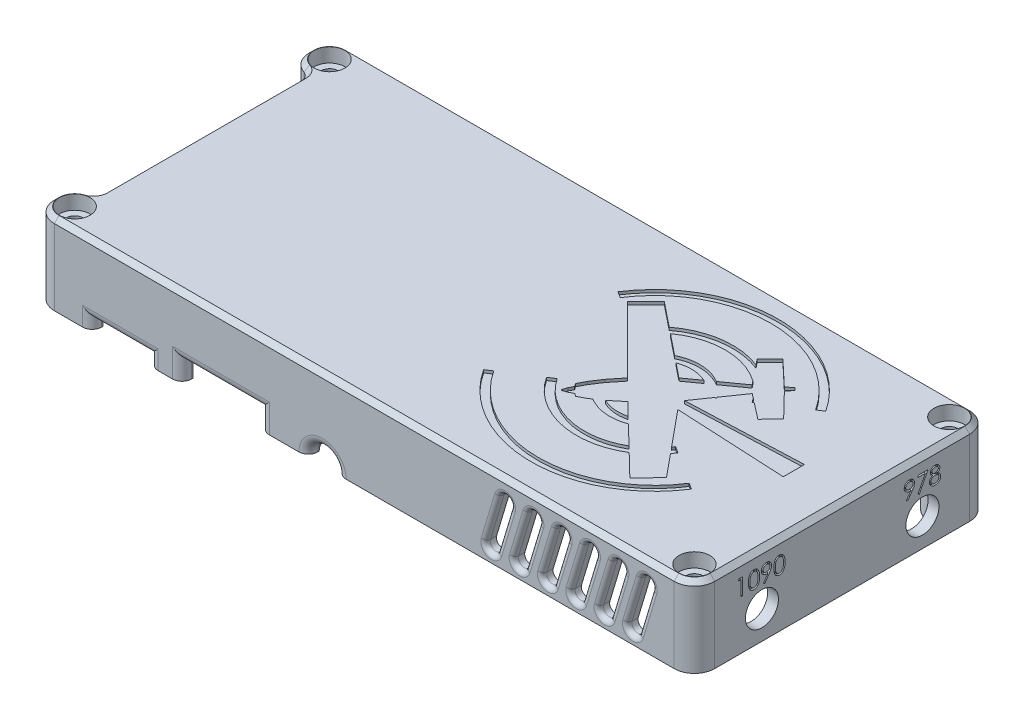
SolidWorks part; units mm, degrees
ref_plane "Front Plane" through (0, 0, 0) normal (0, 0, 1) x (1, 0, 0)
ref_plane "Top Plane" through (0, 0, 0) normal (0, 1, 0) x (1, 0, 0)
ref_plane "Right Plane" through (0, 0, 0) normal (1, 0, 0) x (0, 0, -1)
sketch "Sketch1" plane through (0, 0, 0) normal (0, 1, 0) x (1, 0, 0)
  line L0 (-71.5618, 3.106) -> (57.4382, 3.106) construction
  line L1 (-71.5618, 31.106) -> (57.4382, 31.106)
  line L2 (-71.5618, 31.106) -> (-71.5618, -24.894)
  line L3 (-71.5618, -24.894) -> (57.4382, -24.894)
  line L4 (57.4382, 31.106) -> (57.4382, -24.894)
  line L5 (-60.6618, -24.894) -> (-60.6618, -31.6828) construction
  line L6 (-68.0618, 27.606) -> (-10.0618, 27.606)
  line L7 (-68.0618, 27.606) -> (-68.0618, -21.394)
  line L8 (-68.0618, -21.394) -> (-10.0618, -21.394)
  line L9 (-10.0618, 27.606) -> (-10.0618, -21.394)
  line L10 (-39.5618, -24.894) -> (-39.5618, -31.6828) construction
  line L11 (-18.0618, -24.894) -> (-18.0618, -31.6828) construction
  line L12 (-65.4118, -26.5648) -> (-55.9118, -26.5648) construction
  line L13 (-48.0618, -26.5648) -> (-31.0618, -26.5648) construction
  line L14 (-22.0618, -26.5648) -> (-14.0618, -26.5648) construction
  line L15 (-72.5618, 9.606) -> (-72.5618, -3.394) construction
  line L16 (-71.5618, 3.106) -> (-72.5618, 3.106) construction
  line L17 (-60.6618, -24.894) -> (-60.6618, 40.2849) construction
  dimension "D1" = 129
  dimension "D2" = 56
  dimension "D3" = 49
  dimension "D4" = 58
  dimension "D5" = 3.5
  dimension "D6" = 3.5
  dimension "D7" = 10.9
  dimension "D8" = 32
  dimension "D9" = 53.5
  dimension "D10" = 2
  dimension "D11" = 13
  dimension "D12" = 9.5
  dimension "D13" = 17
  dimension "D14" = 8
sketch "Sketch3" plane through (0, 0, 0) normal (0, 1, 0) x (1, 0, 0)
  line L2 (-72.5618, -25.894) -> (58.4382, -25.894) construction
  line L3 (60.7382, -28.194) -> (60.7382, 34.406) construction
  line L4 (60.7382, 34.406) -> (-74.8618, 34.406)
  line L5 (-74.8618, 34.406) -> (-74.8618, -28.194)
  line L6 (-74.8618, -28.194) -> (60.7382, -28.194)
  line L8 (58.4382, 32.106) -> (-72.5618, 32.106)
  line L9 (58.4382, -25.894) -> (58.4382, 32.106)
  line L10 (-72.5618, -25.894) -> (58.4382, -25.894)
  line L11 (-72.5618, 32.106) -> (-72.5618, -25.894)
  line L12 (58.4382, 32.106) -> (-72.5618, 32.106)
  line L13 (58.4382, -25.894) -> (58.4382, 32.106)
  line L14 (-72.5618, -25.894) -> (58.4382, -25.894)
  line L15 (-72.5618, 32.106) -> (-72.5618, -25.894)
  line L16 (-7.0618, 3.106) -> (-7.0618, 34.406) construction
  line L17 (-71.5618, 3.106) -> (57.4382, 3.106) construction
  line L18 (58.4382, -25.894) -> (58.4382, 32.106) construction
  line L20 (-74.8618, 3.106) -> (52.7382, 3.106) construction
  line L22 (-74.8618, -28.194) -> (60.7382, -28.194) construction
  line L23 (60.7382, -28.194) -> (60.7382, 34.406)
  dimension "D1" = 1
  dimension "D2" = 2.3
extrude "Boss-Extrude1" add sketch "Sketch3" along normal blind 17
sketch "Sketch5" plane through (0, 0, 0) normal (0, 1, 0) x (1, 0, 0)
  line L1 (-72.5618, 32.106) -> (58.4382, 32.106)
  line L2 (-72.5618, 32.106) -> (-72.5618, -25.894)
  line L3 (-72.5618, -25.894) -> (58.4382, -25.894)
  line L4 (58.4382, 32.106) -> (58.4382, -25.894)
sketch "Sketch11" plane through (0, 0, 28.194) normal (0, 0, 1) x (1, 0, 0)
  line L0 (-74.8618, 17) -> (-74.8618, 0) construction
  line L2 (-66.8618, 0) -> (-54.8618, 0)
  line L3 (-66.8618, 0) -> (-66.8618, 2)
  line L4 (-66.8618, 2) -> (-54.8618, 2)
  line L5 (-54.8618, 0) -> (-54.8618, 2)
  line L9 (-47.8118, 4) -> (-31.3118, 4)
  line L10 (-47.8118, 4) -> (-47.8118, 0)
  line L11 (-47.8118, 0) -> (-31.3118, 0)
  line L12 (-31.3118, 4) -> (-31.3118, 0)
  line L14 (-39.5618, 0) -> (-39.528, 10.3) construction
  line L15 (-48.0618, 0) -> (-31.0618, 0) construction
  line L16 (-18.0618, 0) -> (-18.0618, 10.3) construction
  line L17 (-22.0618, 0) -> (-14.0618, 0) construction
  circle A0 centre (-18.0618, 0) radius 3
  dimension "D5" = 6
  dimension "D1" = 4
  dimension "D2" = 2
  dimension "D3" = 12
  dimension "D4" = 16.5
  dimension "D7" = 8
extrude "Cut-Extrude1" cut sketch "Sketch11" against normal up to next
sketch "Sketch14" plane through (0, 0, 0) normal (0, -1, 0) x (1, 0, 0)
  line L1 (-74.8618, 11.894) -> (-72.5618, 11.894)
  line L2 (-74.8618, 11.894) -> (-74.8618, -18.106)
  line L3 (-74.8618, -18.106) -> (-72.5618, -18.106)
  line L4 (-72.5618, 11.894) -> (-72.5618, -18.106)
  dimension "D1" = 30
extrude "Boss-Extrude6" add sketch "Sketch14" along normal blind 2.8
fillet "Fillet6" radius 2 4 edges at (-18.0618, 3, 28.194) (-31.3118, 2, 28.194) (-39.5618, 4, 28.194) (-47.8118, 2, 28.194)
sketch "Sketch15" plane through (-74.8618, 0, 0) normal (-1, 0, 0) x (0, 0, 1)
  line L1 (-9.7403, -3.6489) -> (3.7597, -3.6489)
  line L2 (-9.7403, -3.6489) -> (-9.7403, -2.6489)
  line L3 (-9.7403, -2.6489) -> (3.7597, -2.6489)
  line L4 (3.7597, -3.6489) -> (3.7597, -2.6489)
extrude "Cut-Extrude3" cut sketch "Sketch15" against normal up to next
fillet "Fillet8" radius 2 3 edges at (-74.8618, -2.7245, 3.7597) (-74.8618, -2.7245, -9.7403) (-74.8618, -2.6489, -2.9903)
sketch "Sketch35" plane through (0, 17, 0) normal (0, 1, 0) x (1, 0, 0)
  line L1 (-72.5618, 32.106) -> (58.4382, 32.106)
  line L2 (-72.5618, 32.106) -> (-72.5618, -25.894)
  line L3 (-72.5618, -25.894) -> (58.4382, -25.894)
  line L4 (58.4382, 32.106) -> (58.4382, -25.894)
extrude "Boss-Extrude7" add sketch "Sketch35" against normal blind 2
sketch "Sketch36" plane through (0, 17, 0) normal (0, 1, 0) x (1, 0, 0)
  line L0 (13.7863, -0.484) -> (12.349, -1.4216)
  line L1 (26.8986, -0.4563) -> (28.3399, -1.3879)
  line L2 (13.7684, 8.0304) -> (12.3271, 8.962)
  line L3 (26.8807, 8.058) -> (28.318, 8.9957)
  line L4 (41.0203, -9.5839) -> (42.3245, -10.4269)
  line L5 (32.8559, -4.3068) -> (34.2397, -5.2013)
  line L6 (7.8454, -4.3595) -> (6.4653, -5.2598)
  line L7 (-0.2967, -9.6709) -> (-1.5974, -10.5194)
  line L8 (-0.3532, 17.158) -> (-1.6575, 18.001)
  line L9 (7.8112, 11.8809) -> (6.4273, 12.7754)
  line L10 (32.8217, 11.9336) -> (34.2017, 12.8338)
  line L11 (40.9638, 17.245) -> (42.2645, 18.0935)
  line L12 (49.7971, 1.5668) -> (22.6747, 2.9133)
  line L13 (49.7971, 6.0552) -> (22.6747, 4.9652)
  line L14 (49.7971, 1.5668) -> (49.7971, 6.0552)
  line L15 (22.6747, 2.9133) -> (22.6747, 4.9652)
  arc A0 (42.2645, 18.0935) -> (-1.6575, 18.001) centre (20.3335, 3.787) ccw
  arc A1 (40.9638, 17.245) -> (-0.3532, 17.158) centre (20.3335, 3.787) ccw
  arc A2 (26.8807, 8.058) -> (13.7684, 8.0304) centre (20.3335, 3.787) ccw
  arc A3 (28.318, 8.9957) -> (12.3271, 8.962) centre (20.3335, 3.787) ccw
  arc A4 (34.2017, 12.8338) -> (6.4273, 12.7754) centre (20.3335, 3.787) ccw
  arc A5 (32.8217, 11.9336) -> (7.8112, 11.8809) centre (20.3335, 3.787) ccw
  arc A6 (-1.5974, -10.5194) -> (42.3245, -10.4269) centre (20.3335, 3.787) ccw
  arc A7 (-0.2967, -9.6709) -> (41.0203, -9.5839) centre (20.3335, 3.787) ccw
  arc A8 (6.4653, -5.2598) -> (34.2397, -5.2013) centre (20.3335, 3.787) ccw
  arc A9 (7.8454, -4.3595) -> (32.8559, -4.3068) centre (20.3335, 3.787) ccw
  arc A10 (12.349, -1.4216) -> (28.3399, -1.3879) centre (20.3335, 3.787) ccw
  arc A11 (13.7863, -0.484) -> (26.8986, -0.4563) centre (20.3335, 3.787) ccw
extrude "Cut-Extrude4" cut sketch "Sketch36" against normal blind 0.6
sketch "Sketch37" plane through (0, 17, 0) normal (0, 1, 0) x (1, 0, 0)
  line L0 (19.5432, -1.113) -> (33.7651, -14.904)
  line L1 (33.7651, -14.904) -> (37.5849, -10.9649)
  line L2 (37.5849, -10.9649) -> (24.9049, 4.4162)
  line L3 (24.9049, 4.4162) -> (31.2449, 13.5399)
  line L4 (31.2449, 13.5399) -> (36.5589, 9.4198)
  line L5 (36.5589, 9.4198) -> (39.2481, 12.193)
  line L6 (39.2481, 12.193) -> (34.218, 17.3746)
  line L7 (34.218, 17.3746) -> (35.2171, 18.6632)
  line L8 (35.2171, 18.6632) -> (34.9302, 18.8856)
  line L9 (19.5432, -1.113) -> (16.9215, -3.2743)
  line L10 (16.9215, -3.2743) -> (14.6893, -4.7957)
  line L11 (14.6893, -4.7957) -> (13.0543, -5.6738)
  line L12 (13.0543, -5.6738) -> (12.4225, -5.2348)
  line L13 (12.4225, -5.2348) -> (11.4673, -5.7477)
  line L14 (11.4673, -5.7477) -> (10.605, -6.0351)
  line L15 (10.605, -6.0351) -> (10.3641, -6.0351)
  line L16 (34.9302, 18.8856) -> (10.3641, -6.0351) construction
  line L17 (10.3607, -5.7943) -> (10.3641, -6.0351)
  line L18 (10.6357, -4.9279) -> (10.3607, -5.7943)
  line L19 (11.1349, -3.9655) -> (10.6357, -4.9279)
  line L20 (10.6869, -3.3401) -> (11.1349, -3.9655)
  line L21 (11.5414, -1.6927) -> (10.6869, -3.3401)
  line L22 (13.0306, 0.5611) -> (11.5414, -1.6927)
  line L23 (15.1541, 3.2135) -> (13.0306, 0.5611)
  line L24 (34.7036, 19.1694) -> (34.9302, 18.8856)
  line L25 (33.4295, 18.1519) -> (34.7036, 19.1694)
  line L26 (28.1763, 23.1072) -> (33.4295, 18.1519)
  line L27 (25.4419, 20.3785) -> (28.1763, 23.1072)
  line L28 (29.6378, 15.1241) -> (25.4419, 20.3785)
  line L29 (20.6059, 8.6539) -> (29.6378, 15.1241)
  line L30 (5.0446, 21.1121) -> (20.6059, 8.6539)
  line L31 (1.1607, 17.2363) -> (5.0446, 21.1121)
  line L32 (15.1541, 3.2135) -> (1.1607, 17.2363)
extrude "Cut-Extrude5" cut sketch "Sketch37" against normal blind 0.6
sketch "Sketch48" plane through (0, 17, 0) normal (0, 1, 0) x (1, 0, 0)
  line L0 (-74.8618, -19.594) -> (-74.8618, -28.194)
  line L1 (-74.8618, 34.406) -> (-74.8618, 25.806)
  line L2 (-74.8618, 3.106) -> (-35.5735, 3.106) construction
  line L3 (-74.8618, 34.406) -> (-74.8618, -28.194) construction
  line L4 (60.7382, -28.194) -> (60.7382, 34.406) construction
  arc A0 (-74.8618, -28.194) -> (-74.8618, -19.594) centre (-74.8618, -23.894) cw
  arc A1 (-74.8618, 25.806) -> (-74.8618, 34.406) centre (-74.8618, 30.106) cw
  circle A2 centre (56.4382, 30.106) radius 4.3
  circle A3 centre (56.4382, -23.894) radius 4.3
  dimension "D1" = 4.3
extrude "Boss-Extrude9" add sketch "Sketch48" against normal up to vertex
hole_wizard "CBORE for M3 SHCS1" positions "Sketch50" profile "Sketch49" counterbore size "M3" standard "ANSI Metric" end condition up to next
sketch "Sketch50" plane through (0, 17, 0) normal (0, 1, 0) x (1, 0, 0)
  point P0 (-74.8618, 30.106)
sketch "Sketch49" plane through (-74.8618, 17, -30.106) normal (1, 0, 0) x (0, 0, 1)
  line L0 (0, 0) -> (0, 17)
  line L1 (0, 17) -> (1.8, 17)
  line L3 (1.8, 17) -> (1.8, 3)
  line L4 (1.8, 3) -> (3.25, 3)
  line L5 (3.25, 3) -> (3.25, 0)
  line L7 (3.25, 0) -> (0, 0)
  line L11 (0, -6.35) -> (0, 107.95) construction
  dimension "Thru Hole Dia." = 3.6
  dimension "Thru Hole Depth" = 17
  dimension "C'Bore Dia." = 6.5
  dimension "C'Bore Depth" = 3
hole_wizard "CBORE for M3 SHCS2" positions "Sketch52" profile "Sketch51" counterbore size "M3" standard "ANSI Metric" end condition up to next
sketch "Sketch52" plane through (0, 17, 0) normal (0, 1, 0) x (1, 0, 0)
  point P0 (-74.8618, -23.894)
sketch "Sketch51" plane through (-74.8618, 17, 23.894) normal (1, 0, 0) x (0, 0, 1)
  line L0 (0, 0) -> (0, 17)
  line L1 (0, 17) -> (1.8, 17)
  line L3 (1.8, 17) -> (1.8, 3)
  line L4 (1.8, 3) -> (3.25, 3)
  line L5 (3.25, 3) -> (3.25, 0)
  line L7 (3.25, 0) -> (0, 0)
  line L11 (0, -6.35) -> (0, 107.95) construction
  dimension "Thru Hole Dia." = 3.6
  dimension "Thru Hole Depth" = 17
  dimension "C'Bore Dia." = 6.5
  dimension "C'Bore Depth" = 3
fillet "Fillet13" radius 2 2 edges at (-74.8618, 8.5, 19.594) (-74.8618, 8.5, -25.806)
chamfer "Chamfer1" distance 1 angle 45 1 edges at (-9.8342, 15, -32.106)
chamfer "Chamfer3" distance 1 angle 45 7 edges at (-7.0618, 17, -34.406) (-79.1058, 17, -30.7975) (-74.8618, 17, -3.106) (-79.1058, 17, 24.5855) (-75.2385, 17, 19.0883) (-75.2385, 17, -25.3002) (-7.0618, 17, 28.194)
fillet "Fillet14" radius 2 3 edges at (-66.8618, 1, 28.194) (-60.8618, 2, 28.194) (-54.8618, 1, 28.194)
sketch "Sketch58" plane through (-74.8618, 0, 0) normal (-1, 0, 0) x (0, 0, 1)
  line L0 (-19.9832, 3.4697) -> (-16.3616, 12.7909) construction
  line L1 (-21.1484, 3.9224) -> (-17.5268, 13.2436)
  line L2 (-18.8181, 3.017) -> (-15.1965, 12.3382)
  line L3 (-13.9832, 3.4697) -> (-10.3616, 12.7909) construction
  line L4 (-15.1484, 3.9224) -> (-11.5268, 13.2436)
  line L5 (-12.8181, 3.017) -> (-9.1965, 12.3382)
  line L6 (-7.9832, 3.4697) -> (-4.3616, 12.7909) construction
  line L7 (-9.1484, 3.9224) -> (-5.5268, 13.2436)
  line L8 (-6.8181, 3.017) -> (-3.1965, 12.3382)
  line L9 (-1.9832, 3.4697) -> (1.6384, 12.7909) construction
  line L10 (-3.1484, 3.9224) -> (0.4732, 13.2436)
  line L11 (-0.8181, 3.017) -> (2.8035, 12.3382)
  line L12 (4.0168, 3.4697) -> (7.6384, 12.7909) construction
  line L13 (2.8516, 3.9224) -> (6.4732, 13.2436)
  line L14 (5.1819, 3.017) -> (8.8035, 12.3382)
  line L15 (10.0168, 3.4697) -> (13.6384, 12.7909) construction
  line L16 (8.8516, 3.9224) -> (12.4732, 13.2436)
  line L17 (11.1819, 3.017) -> (14.8035, 12.3382)
  arc A0 (-21.1484, 3.9224) -> (-18.8181, 3.017) centre (-19.9832, 3.4697) ccw
  arc A1 (-15.1965, 12.3382) -> (-17.5268, 13.2436) centre (-16.3616, 12.7909) ccw
  arc A2 (-15.1484, 3.9224) -> (-12.8181, 3.017) centre (-13.9832, 3.4697) ccw
  arc A3 (-9.1965, 12.3382) -> (-11.5268, 13.2436) centre (-10.3616, 12.7909) ccw
  arc A4 (-9.1484, 3.9224) -> (-6.8181, 3.017) centre (-7.9832, 3.4697) ccw
  arc A5 (-3.1965, 12.3382) -> (-5.5268, 13.2436) centre (-4.3616, 12.7909) ccw
  arc A6 (-3.1484, 3.9224) -> (-0.8181, 3.017) centre (-1.9832, 3.4697) ccw
  arc A7 (2.8035, 12.3382) -> (0.4732, 13.2436) centre (1.6384, 12.7909) ccw
  arc A8 (2.8516, 3.9224) -> (5.1819, 3.017) centre (4.0168, 3.4697) ccw
  arc A9 (8.8035, 12.3382) -> (6.4732, 13.2436) centre (7.6384, 12.7909) ccw
  arc A10 (8.8516, 3.9224) -> (11.1819, 3.017) centre (10.0168, 3.4697) ccw
  arc A11 (14.8035, 12.3382) -> (12.4732, 13.2436) centre (13.6384, 12.7909) ccw
  point P2 (-18.1724, 8.1303)
  point P10 (-12.1724, 8.1303)
  point P17 (-6.1724, 8.1303)
  point P24 (-0.1724, 8.1303)
  point P31 (5.8276, 8.1303)
  point P38 (11.8276, 8.1303)
  dimension "D1" = 6
fillet "Fillet15" radius 4.3 2 edges at (60.7382, 8, -34.406) (60.7382, 8, 28.194)
hole_wizard "CBORE for M3 SHCS4" positions "Sketch62" profile "Sketch61" counterbore size "M3" standard "ANSI Metric" end condition up to next
sketch "Sketch62" plane through (0, 17, 0) normal (0, 1, 0) x (1, 0, 0)
  point P0 (56.4382, 30.106)
sketch "Sketch61" plane through (56.4382, 17, -30.106) normal (1, 0, 0) x (0, 0, 1)
  line L0 (0, 0) -> (0, 17)
  line L1 (0, 17) -> (1.8, 17)
  line L3 (1.8, 17) -> (1.8, 3)
  line L4 (1.8, 3) -> (3.25, 3)
  line L5 (3.25, 3) -> (3.25, 0)
  line L7 (3.25, 0) -> (0, 0)
  line L11 (0, -6.35) -> (0, 107.95) construction
  dimension "Thru Hole Dia." = 3.6
  dimension "Thru Hole Depth" = 17
  dimension "C'Bore Dia." = 6.5
  dimension "C'Bore Depth" = 3
hole_wizard "CBORE for M3 SHCS5" positions "Sketch64" profile "Sketch63" counterbore size "M3" standard "ANSI Metric" end condition up to next
sketch "Sketch64" plane through (0, 17, 0) normal (0, 1, 0) x (1, 0, 0)
  point P0 (56.4382, -23.894)
sketch "Sketch63" plane through (56.4382, 17, 23.894) normal (1, 0, 0) x (0, 0, 1)
  line L0 (0, 0) -> (0, 17)
  line L1 (0, 17) -> (1.8, 17)
  line L3 (1.8, 17) -> (1.8, 3)
  line L4 (1.8, 3) -> (3.25, 3)
  line L5 (3.25, 3) -> (3.25, 0)
  line L7 (3.25, 0) -> (0, 0)
  line L11 (0, -6.35) -> (0, 107.95) construction
  dimension "Thru Hole Dia." = 3.6
  dimension "Thru Hole Depth" = 17
  dimension "C'Bore Dia." = 6.5
  dimension "C'Bore Depth" = 3
chamfer "Chamfer7" distance 1 angle 45 5 edges at (60.7382, 17, -3.106) (60.3334, 17, 25.7155) (60.3334, 17, -31.9275) (57.9045, 16.2577, -34.1483) (57.9045, 16.2577, 27.9363)
sketch "Sketch67" plane through (0, 0, 28.194) normal (0, 0, 1) x (1, 0, 0)
  line L0 (44.5955, 12.4849) -> (41.7225, 2.9065) construction
  line L1 (45.7928, 12.1258) -> (42.9198, 2.5474)
  line L2 (43.3981, 12.8441) -> (40.5252, 3.2656)
  line L3 (38.5955, 12.4849) -> (35.7225, 2.9065) construction
  line L4 (39.7928, 12.1258) -> (36.9198, 2.5474)
  line L5 (37.3981, 12.8441) -> (34.5252, 3.2656)
  line L6 (32.5955, 12.4849) -> (29.7225, 2.9065) construction
  line L7 (33.7928, 12.1258) -> (30.9198, 2.5474)
  line L8 (31.3981, 12.8441) -> (28.5252, 3.2656)
  line L9 (26.5955, 12.4849) -> (23.7225, 2.9065) construction
  line L10 (27.7928, 12.1258) -> (24.9198, 2.5474)
  line L11 (25.3981, 12.8441) -> (22.5252, 3.2656)
  line L12 (50.5955, 12.4849) -> (47.7225, 2.9065) construction
  line L13 (51.7928, 12.1258) -> (48.9198, 2.5474)
  line L14 (49.3981, 12.8441) -> (46.5252, 3.2656)
  line L15 (20.5955, 12.4849) -> (17.7225, 2.9065) construction
  line L16 (21.7928, 12.1258) -> (18.9198, 2.5474)
  line L17 (19.3981, 12.8441) -> (16.5252, 3.2656)
  arc A0 (45.7928, 12.1258) -> (43.3981, 12.8441) centre (44.5955, 12.4849) ccw
  arc A1 (40.5252, 3.2656) -> (42.9198, 2.5474) centre (41.7225, 2.9065) ccw
  arc A2 (39.7928, 12.1258) -> (37.3981, 12.8441) centre (38.5955, 12.4849) ccw
  arc A3 (34.5252, 3.2656) -> (36.9198, 2.5474) centre (35.7225, 2.9065) ccw
  arc A4 (33.7928, 12.1258) -> (31.3981, 12.8441) centre (32.5955, 12.4849) ccw
  arc A5 (28.5252, 3.2656) -> (30.9198, 2.5474) centre (29.7225, 2.9065) ccw
  arc A6 (27.7928, 12.1258) -> (25.3981, 12.8441) centre (26.5955, 12.4849) ccw
  arc A7 (22.5252, 3.2656) -> (24.9198, 2.5474) centre (23.7225, 2.9065) ccw
  arc A8 (51.7928, 12.1258) -> (49.3981, 12.8441) centre (50.5955, 12.4849) ccw
  arc A9 (46.5252, 3.2656) -> (48.9198, 2.5474) centre (47.7225, 2.9065) ccw
  arc A10 (21.7928, 12.1258) -> (19.3981, 12.8441) centre (20.5955, 12.4849) ccw
  arc A11 (16.5252, 3.2656) -> (18.9198, 2.5474) centre (17.7225, 2.9065) ccw
  point P3 (43.159, 7.6957)
  point P10 (37.159, 7.6957)
  point P17 (31.159, 7.6957)
  point P24 (25.159, 7.6957)
  point P30 (49.159, 7.6957)
  point P38 (19.159, 7.6957)
  dimension "D1" = 6
sketch "Sketch68" plane through (60.7382, 0, 0) normal (1, 0, 0) x (0, 0, -1)
  line L0 (-23.894, 6) -> (30.106, 6) construction
  line L1 (-23.894, 16) -> (-23.894, 0) construction
  line L2 (30.106, 0) -> (30.106, 16) construction
  line L3 (-23.894, 0) -> (30.106, 0) construction
  circle A0 centre (-13.894, 6) radius 3.5
  circle A1 centre (20.106, 6) radius 3.5
  dimension "D1" = 10
  dimension "D2" = 10
  dimension "D3" = 6
extrude "Cut-Extrude19" cut sketch "Sketch68" against normal up to next
sketch "Sketch69" plane through (60.7382, 0, 0) normal (1, 0, 0) x (0, 0, -1)
  line L0 (-19.5849, 10.4138) -> (-8.2031, 10.4138) construction
  line L1 (14.0086, 10.4138) -> (26.2034, 10.4138) construction
  text T0 "1090"
  text T1 "978"
extrude "Cut-Extrude20" cut sketch "Sketch69" against normal blind 0.5
extrude "Cut-Extrude21" cut sketch "Sketch58" against normal up to next
fillet "Fillet16" radius 1 24 edges at (-74.8618, 13.956, -15.9089) (-74.8618, 7.6776, -17.0073) (-74.8618, 2.3046, -20.4359) (-74.8618, 8.583, -19.3376) (-74.8618, 13.956, 14.0911) (-74.8618, 7.6776, 12.9927) (-74.8618, 2.3046, 9.5641) (-74.8618, 13.956, 8.0911) (-74.8618, 7.6776, 6.9927) (-74.8618, 2.3046, 3.5641) (-74.8618, 13.956, 2.0911) (-74.8618, 7.6776, 0.9927) (-74.8618, 2.3046, -2.4359) (-74.8618, 13.956, -3.9089) (-74.8618, 7.6776, -5.0073) (-74.8618, 2.3046, -8.4359) (-74.8618, 13.956, -9.9089) (-74.8618, 7.6776, -11.0073) (-74.8618, 2.3046, -14.4359) (-74.8618, 8.583, 10.6624) (-74.8618, 8.583, 4.6624) (-74.8618, 8.583, -1.3376) (-74.8618, 8.583, -7.3376) (-74.8618, 8.583, -13.3376)
extrude "Cut-Extrude22" cut sketch "Sketch67" against normal through all
fillet "Fillet17" radius 1 48 edges at (50.9546, 13.6822, -34.406) (50.3563, 7.3366, -34.406) (47.3633, 1.7092, -34.406) (50.9546, 13.6822, 28.194) (50.3563, 7.3366, 28.194) (47.3633, 1.7092, 28.194) (47.9617, 8.0548, -34.406) (47.9617, 8.0548, 28.194) (44.9546, 13.6822, -34.406) (44.3563, 7.3366, -34.406) (41.3633, 1.7092, -34.406) (38.9546, 13.6822, -34.406) (38.3563, 7.3366, -34.406) (35.3633, 1.7092, -34.406) (32.9546, 13.6822, -34.406) (32.3563, 7.3366, -34.406) (29.3633, 1.7092, -34.406) (26.9546, 13.6822, -34.406) (26.3563, 7.3366, -34.406) (23.3633, 1.7092, -34.406) (20.9546, 13.6822, -34.406) (20.3563, 7.3366, -34.406) (17.3633, 1.7092, -34.406) (44.9546, 13.6822, 28.194) (44.3563, 7.3366, 28.194) (41.3633, 1.7092, 28.194) (38.9546, 13.6822, 28.194) (38.3563, 7.3366, 28.194) (35.3633, 1.7092, 28.194) (32.9546, 13.6822, 28.194) (32.3563, 7.3366, 28.194) (29.3633, 1.7092, 28.194) (26.9546, 13.6822, 28.194) (26.3563, 7.3366, 28.194) (23.3633, 1.7092, 28.194) (20.9546, 13.6822, 28.194) (20.3563, 7.3366, 28.194) (17.3633, 1.7092, 28.194) (41.9617, 8.0548, -34.406) (35.9617, 8.0548, -34.406) (29.9617, 8.0548, -34.406) (23.9617, 8.0548, -34.406) (17.9617, 8.0548, -34.406) (41.9617, 8.0548, 28.194) (35.9617, 8.0548, 28.194) (29.9617, 8.0548, 28.194) (23.9617, 8.0548, 28.194) (17.9617, 8.0548, 28.194)
